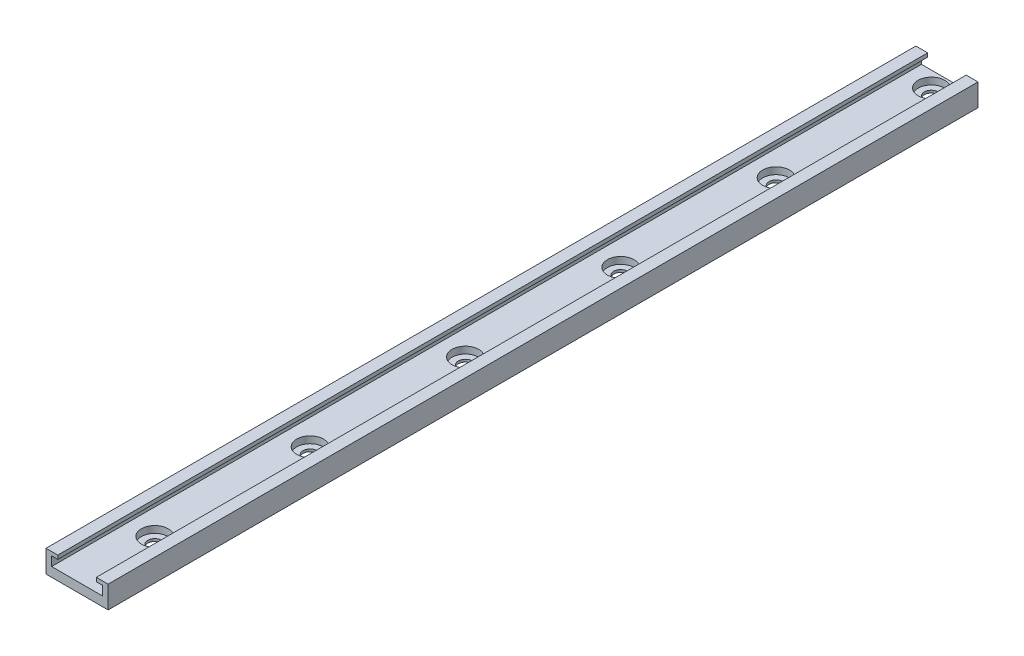
SolidWorks part; units mm, degrees
ref_plane "正面" through (0, 0, 0) normal (0, 0, 1) x (1, 0, 0)
ref_plane "平面" through (0, 0, 0) normal (0, 1, 0) x (1, 0, 0)
ref_plane "右側面" through (0, 0, 0) normal (1, 0, 0) x (0, 0, -1)
sketch "ｽｹｯﾁ1" plane through (0, 0, 0) normal (0, 0, 1) x (1, 0, 0)
  line L0 (0, 0) -> (20, 0)
  line L1 (20, 0) -> (20, 7.2)
  line L2 (20, 7.2) -> (16.2, 7.2)
  line L3 (16.2, 7.2) -> (16.2, 5.9697)
  line L4 (16.2, 5.9697) -> (18.2, 5.9697)
  line L5 (18.2, 5.9697) -> (18.2, 3)
  line L6 (18.2, 3) -> (1.8, 3)
  line L7 (1.8, 3) -> (1.8, 6)
  line L8 (1.8, 6) -> (3.8, 6)
  line L9 (3.8, 6) -> (3.8, 7.2)
  line L10 (3.8, 7.2) -> (0, 7.2)
  line L11 (0, 7.2) -> (0, 0)
  dimension "D1" = 20
  dimension "D2" = 7.2
  dimension "D3" = 3
  dimension "D4" = 3.8
  dimension "D5" = 3.8
  dimension "D6" = 2
  dimension "D7" = 2
  dimension "D8" = 3
extrude "ﾎﾞｽ - 押し出し2" add sketch "ｽｹｯﾁ1" along normal blind 280 contours L6 L7 L8 L9 L10 L11 L0 L1 L2 L3 L4 L5
hole_wizard "M4 丸押えねじ用座ぐり穴1" positions "ｽｹｯﾁ3" profile "ｽｹｯﾁ2" counterbore size "M4" standard "JIS" end condition through all
sketch "ｽｹｯﾁ3" plane through (0, 3, 0) normal (0, 1, 0) x (1, 0, 0)
  line L0 (18.2, -280) -> (1.8, -280) construction
  line L1 (0, -280) -> (0, 0) construction
  line L2 (0, 0) -> (20, 0) construction
  line L3 (20, -280) -> (20, 0) construction
  point P0 (10, -255)
  point P2 (10, -205)
  point P4 (10, -155)
  point P6 (10, -105)
  point P8 (10, -55)
  dimension "D1" = 25
  dimension "D2" = 50
  dimension "D3" = 50
  dimension "D4" = 50
  dimension "D5" = 50
  dimension "D6" = 10
  dimension "D7" = 10
  dimension "D8" = 10
  dimension "D9" = 55
sketch "ｽｹｯﾁ2" plane through (10, 3, 255) normal (1, 0, 0) x (0, 0, 1)
  line L0 (0, 0) -> (0, 3)
  line L1 (0, 3) -> (2.25, 3)
  line L3 (2.25, 3) -> (2.25, 2.2)
  line L4 (2.25, 2.2) -> (4.3, 2.2)
  line L5 (4.3, 2.2) -> (4.3, 0)
  line L7 (4.3, 0) -> (0, 0)
  line L11 (0, -6.35) -> (0, 107.95) construction
  dimension "通し穴の直径" = 4.5
  dimension "通し穴の深さ" = 3
  dimension "座ぐり穴の直径" = 8.6
  dimension "座ぐり穴の深さ" = 2.2
hole_wizard "M4 丸押えねじ用座ぐり穴3" positions "ｽｹｯﾁ7" profile "ｽｹｯﾁ6" counterbore size "M4" standard "JIS" end condition through all
sketch "ｽｹｯﾁ7" plane through (0, 3, 0) normal (0, 1, 0) x (1, 0, 0)
  line L0 (18.2, 0) -> (1.8, 0) construction
  line L1 (0, -280) -> (0, 0) construction
  point P0 (10, -5)
  dimension "D1" = 5
  dimension "D2" = 10
sketch "ｽｹｯﾁ6" plane through (10, 3, 5) normal (1, 0, 0) x (0, 0, 1)
  line L0 (0, 0) -> (0, 3)
  line L1 (0, 3) -> (2.25, 3)
  line L3 (2.25, 3) -> (2.25, 2.2)
  line L4 (2.25, 2.2) -> (4.3, 2.2)
  line L5 (4.3, 2.2) -> (4.3, 0)
  line L7 (4.3, 0) -> (0, 0)
  line L11 (0, -6.35) -> (0, 107.95) construction
  dimension "通し穴の直径" = 4.5
  dimension "通し穴の深さ" = 3
  dimension "座ぐり穴の直径" = 8.6
  dimension "座ぐり穴の深さ" = 2.2
